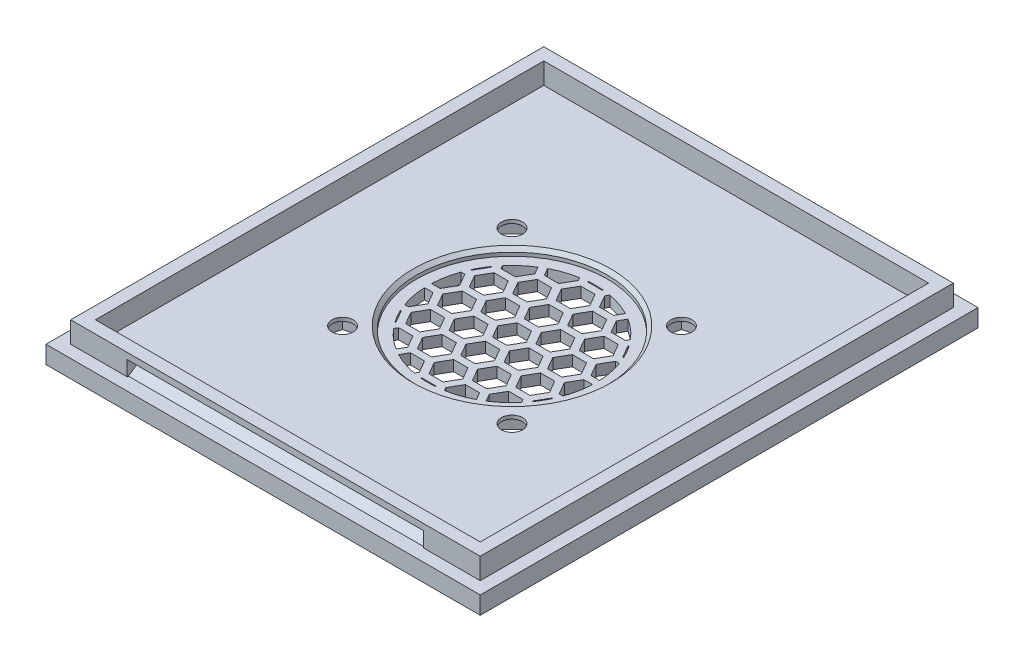
SolidWorks part; units mm, degrees
ref_plane "Front Plane" through (0, 0, 0) normal (0, 0, 1) x (1, 0, 0)
ref_plane "Top Plane" through (0, 0, 0) normal (0, 1, 0) x (1, 0, 0)
ref_plane "Right Plane" through (0, 0, 0) normal (1, 0, 0) x (0, 0, -1)
sketch "Sketch1" plane through (0, 0, 0) normal (0, 1, 0) x (1, 0, 0)
  line L0 (-15, 12) -> (-15, -12) construction
  line L1 (-30.75, -35.25) -> (30.75, -35.25)
  line L2 (-30.75, -35.25) -> (-30.75, 35.25)
  line L3 (-30.75, 35.25) -> (30.75, 35.25)
  line L4 (30.75, -35.25) -> (30.75, 35.25)
  line L5 (-30.75, -35.25) -> (30.75, 35.25) construction
  line L6 (-30.75, 35.25) -> (30.75, -35.25) construction
  line L7 (-12, -15) -> (12, -15) construction
  line L8 (15, -12) -> (15, 12) construction
  line L9 (12, 15) -> (-12, 15) construction
  line L10 (-15, 12) -> (-15, -12) construction
  line L11 (-12, -15) -> (12, -15) construction
  line L12 (15, -12) -> (15, 12) construction
  line L13 (12, 15) -> (-12, 15) construction
  arc A0 (14.2149, 1) -> (-6.2414, 12.8104) centre (0, 0) ccw construction
  arc A1 (-7.9735, 11.8104) -> (-7.9735, -11.8104) centre (0, 0) ccw construction
  arc A2 (-6.2414, -12.8104) -> (14.2149, -1) centre (0, 0) ccw construction
  arc A3 (14.2149, 1) -> (-6.2414, 12.8104) centre (0, 0) ccw construction
  arc A4 (-7.9735, 11.8104) -> (-7.9735, -11.8104) centre (0, 0) ccw construction
  arc A5 (-6.2414, -12.8104) -> (14.2149, -1) centre (0, 0) ccw construction
  arc A6 (-12, 15) -> (-15, 12) centre (-12, 12) ccw construction
  arc A7 (-15, -12) -> (-12, -15) centre (-12, -12) ccw construction
  arc A8 (12, -15) -> (15, -12) centre (12, -12) ccw construction
  arc A9 (15, 12) -> (12, 15) centre (12, 12) ccw construction
  arc A10 (-12, 15) -> (-15, 12) centre (-12, 12) ccw construction
  arc A11 (-15, -12) -> (-12, -15) centre (-12, -12) ccw construction
  arc A12 (12, -15) -> (15, -12) centre (12, -12) ccw construction
  arc A13 (15, 12) -> (12, 15) centre (12, 12) ccw construction
  circle A18 centre (12, 12) radius 1.5 construction
  circle A19 centre (12, -12) radius 1.5 construction
  circle A20 centre (-12, -12) radius 1.5 construction
  circle A21 centre (-12, 12) radius 1.5 construction
  circle A22 centre (-12, 12) radius 1.5
  circle A23 centre (-12, -12) radius 1.5
  circle A24 centre (12, -12) radius 1.5
  circle A25 centre (12, 12) radius 1.5
  point P0 (0, 0)
  dimension "D1" = 70.5
  dimension "D2" = 61.5
extrude "Boss-Extrude1" add sketch "Sketch1" along normal blind 2.5
ref_axis "Axis1" through (0, 0, 0) along (0, 0, 1)
sketch "Sketch2" plane through (0, 2.5, 0) normal (0, 1, 0) x (1, 0, 0)
  line L20 (27.25, -31.75) -> (27.25, 31.75)
  line L21 (27.25, 31.75) -> (-27.25, 31.75)
  line L22 (-27.25, 31.75) -> (-27.25, -31.75)
  line L23 (-27.25, -31.75) -> (27.25, -31.75)
  line L24 (-29, -33.5) -> (29, -33.5)
  line L25 (29, -33.5) -> (29, 33.5)
  line L26 (-29, 33.5) -> (-29, -33.5)
  line L27 (29, 33.5) -> (-29, 33.5)
  line L28 (-29, -33.5) -> (29, -33.5)
  line L29 (29, -33.5) -> (29, 33.5)
  line L30 (-29, 33.5) -> (-29, -33.5)
  line L31 (29, 33.5) -> (-29, 33.5)
  dimension "D1" = 1.75
  dimension "D2" = 1.75
extrude "Boss-Extrude2" add sketch "Sketch2" along normal blind 3
sketch "Sketch3" plane through (0, 0, 0) normal (0, -1, 0) x (1, 0, 0)
  line L1 (-11.2529, 9.2116) -> (-9.2116, 11.2529)
  line L2 (-9.2116, 11.2529) -> (-9.9588, 14.0412)
  line L3 (-9.9588, 14.0412) -> (-12.7471, 14.7884)
  line L4 (-12.7471, 14.7884) -> (-14.7884, 12.7471)
  line L5 (-14.7884, 12.7471) -> (-14.0412, 9.9588)
  line L6 (-14.0412, 9.9588) -> (-11.2529, 9.2116)
  line L7 (0, 0) -> (-6.0112, 6.0112) construction
  line L8 (9.2116, 11.2529) -> (11.2529, 9.2116)
  line L9 (11.2529, 9.2116) -> (14.0412, 9.9588)
  line L10 (14.0412, 9.9588) -> (14.7884, 12.7471)
  line L11 (14.7884, 12.7471) -> (12.7471, 14.7884)
  line L12 (12.7471, 14.7884) -> (9.9588, 14.0412)
  line L13 (9.9588, 14.0412) -> (9.2116, 11.2529)
  line L14 (11.2529, -9.2116) -> (9.2116, -11.2529)
  line L15 (9.2116, -11.2529) -> (9.9588, -14.0412)
  line L16 (9.9588, -14.0412) -> (12.7471, -14.7884)
  line L17 (12.7471, -14.7884) -> (14.7884, -12.7471)
  line L18 (14.7884, -12.7471) -> (14.0412, -9.9588)
  line L19 (14.0412, -9.9588) -> (11.2529, -9.2116)
  line L20 (-9.2116, -11.2529) -> (-11.2529, -9.2116)
  line L21 (-11.2529, -9.2116) -> (-14.0412, -9.9588)
  line L22 (-14.0412, -9.9588) -> (-14.7884, -12.7471)
  line L23 (-14.7884, -12.7471) -> (-12.7471, -14.7884)
  line L24 (-12.7471, -14.7884) -> (-9.9588, -14.0412)
  line L25 (-9.9588, -14.0412) -> (-9.2116, -11.2529)
  line L26 (0, 0) -> (-9.2116, 0) construction
  circle A0 centre (-12, 12) radius 2.5 construction
  circle A1 centre (0, 0) radius 12.2353 construction
  circle A2 centre (12, 12) radius 2.5 construction
  circle A3 centre (12, -12) radius 2.5 construction
  circle A4 centre (-12, -12) radius 2.5 construction
  circle A5 centre (12, 12) radius 1.5 construction
  point P39 (0, 0)
  dimension "D1" = 5
  dimension "D2" = 4
  dimension "D3" = 45
extrude "Cut-Extrude1" cut sketch "Sketch3" against normal blind 2
sketch "Sketch4" plane through (0, 0, 0) normal (0, -1, 0) x (1, 0, 0)
  line L0 (2.0207, 4.5) -> (1.0104, 6.25)
  line L7 (2.0207, 0) -> (1.0104, 1.75)
  line L8 (1.0104, 1.75) -> (-1.0104, 1.75)
  line L9 (-1.0104, 1.75) -> (-2.0207, 0)
  line L16 (-2.0207, 0) -> (-1.0104, -1.75)
  line L17 (-1.0104, -1.75) -> (1.0104, -1.75)
  line L18 (1.0104, -1.75) -> (2.0207, 0)
  line L27 (1.0104, 6.25) -> (-1.0104, 6.25)
  line L96 (-1.0104, 6.25) -> (-2.0207, 4.5)
  line L97 (-2.0207, 4.5) -> (-1.0104, 2.75)
  line L98 (-1.0104, 2.75) -> (1.0104, 2.75)
  line L101 (1.0104, 2.75) -> (2.0207, 4.5)
  line L102 (2.0207, 9) -> (1.0104, 10.75)
  line L103 (1.0104, 10.75) -> (-1.0104, 10.75)
  line L124 (-1.0104, 10.75) -> (-2.0207, 9)
  line L125 (-2.0207, 9) -> (-1.0104, 7.25)
  line L126 (-1.0104, 7.25) -> (1.0104, 7.25)
  line L128 (1.0104, 7.25) -> (2.0207, 9)
  line L133 (-1.0722, 11.8572) -> (-1.0104, 11.75)
  line L146 (-1.0104, 11.75) -> (1.0104, 11.75)
  line L147 (1.0104, 11.75) -> (1.0722, 11.8572)
  line L162 (2.0207, -4.5) -> (1.0104, -2.75)
  line L170 (1.0104, -2.75) -> (-1.0104, -2.75)
  line L177 (-1.0104, -2.75) -> (-2.0207, -4.5)
  line L185 (-2.0207, -4.5) -> (-1.0104, -6.25)
  line L187 (-1.0104, -6.25) -> (1.0104, -6.25)
  line L194 (1.0104, -6.25) -> (2.0207, -4.5)
  line L210 (2.0207, -9) -> (1.0104, -7.25)
  line L237 (1.0104, -7.25) -> (-1.0104, -7.25)
  line L239 (-1.0104, -7.25) -> (-2.0207, -9)
  line L263 (-2.0207, -9) -> (-1.0104, -10.75)
  line L407 (-1.0104, -10.75) -> (1.0104, -10.75)
  line L408 (1.0104, -10.75) -> (2.0207, -9)
  line L409 (1.0722, -11.8572) -> (1.0104, -11.75)
  line L411 (1.0104, -11.75) -> (-1.0104, -11.75)
  line L412 (-1.0104, -11.75) -> (-1.0722, -11.8572)
  line L443 (-2.0207, 0) -> (2.0207, 0)
  line L451 (9.8147, 4.5) -> (8.8044, 6.25)
  line L458 (9.8147, 0) -> (8.8044, 1.75)
  line L466 (8.8044, 1.75) -> (6.7836, 1.75)
  line L691 (6.7836, 1.75) -> (5.7733, 0)
  line L726 (5.7733, 0) -> (6.7836, -1.75)
  line L734 (6.7836, -1.75) -> (8.8044, -1.75)
  line L741 (8.8044, -1.75) -> (9.8147, 0)
  line L749 (8.8044, 6.25) -> (6.7836, 6.25)
  line L757 (6.7836, 6.25) -> (5.7733, 4.5)
  line L777 (5.7733, 4.5) -> (6.7836, 2.75)
  line L786 (6.7836, 2.75) -> (8.8044, 2.75)
  line L826 (8.8044, 2.75) -> (9.8147, 4.5)
  line L854 (6.3804, 10.0515) -> (5.7733, 9)
  line L861 (5.7733, 9) -> (6.7836, 7.25)
  line L862 (6.7836, 7.25) -> (8.8044, 7.25)
  line L863 (8.8044, 7.25) -> (9.0707, 7.7113)
  line L947 (9.8147, -4.5) -> (8.8044, -2.75)
  line L949 (8.8044, -2.75) -> (6.7836, -2.75)
  line L952 (6.7836, -2.75) -> (5.7733, -4.5)
  line L954 (5.7733, -4.5) -> (6.7836, -6.25)
  line L973 (6.7836, -6.25) -> (8.8044, -6.25)
  line L974 (8.8044, -6.25) -> (9.8147, -4.5)
  line L975 (9.0707, -7.7113) -> (8.8044, -7.25)
  line L977 (8.8044, -7.25) -> (6.7836, -7.25)
  line L978 (6.7836, -7.25) -> (5.7733, -9)
  line L979 (5.7733, -9) -> (6.3804, -10.0515)
  line L1151 (17.6087, 4.5) -> (16.5984, 6.25) [skipped]
  line L1152 (16.5984, 6.25) -> (14.5776, 6.25) [skipped]
  line L1153 (14.5776, 6.25) -> (13.5673, 4.5) [skipped]
  line L1154 (13.5673, 4.5) -> (14.5776, 2.75) [skipped]
  line L1155 (16.5984, 2.75) -> (17.6087, 4.5) [skipped]
  line L1156 (17.6087, 9) -> (16.5984, 10.75) [skipped]
  line L1157 (16.5984, 10.75) -> (14.5776, 10.75) [skipped]
  line L1158 (14.5776, 10.75) -> (13.5673, 9) [skipped]
  line L1159 (13.5673, 9) -> (14.5776, 7.25) [skipped]
  line L1160 (14.5776, 7.25) -> (16.5984, 7.25) [skipped]
  line L1161 (16.5984, 7.25) -> (17.6087, 9) [skipped]
  line L1165 (13.5673, 13.5) -> (14.5776, 11.75) [skipped]
  line L1166 (14.5776, 11.75) -> (16.5984, 11.75) [skipped]
  line L1167 (16.5984, 11.75) -> (17.6087, 13.5) [skipped]
  line L1168 (14.5776, 2.75) -> (16.5984, 2.75) [skipped]
  line L1169 (17.6087, -4.5) -> (16.5984, -2.75) [skipped]
  line L1170 (16.5984, -2.75) -> (14.5776, -2.75) [skipped]
  line L1171 (14.5776, -2.75) -> (13.5673, -4.5) [skipped]
  line L1172 (13.5673, -4.5) -> (14.5776, -6.25) [skipped]
  line L1173 (14.5776, -6.25) -> (16.5984, -6.25) [skipped]
  line L1174 (16.5984, -6.25) -> (17.6087, -4.5) [skipped]
  line L1175 (17.6087, -9) -> (16.5984, -7.25) [skipped]
  line L1176 (16.5984, -7.25) -> (14.5776, -7.25) [skipped]
  line L1177 (14.5776, -7.25) -> (13.5673, -9) [skipped]
  line L1178 (13.5673, -9) -> (14.5776, -10.75) [skipped]
  line L1179 (14.5776, -10.75) -> (16.5984, -10.75) [skipped]
  line L1180 (16.5984, -10.75) -> (17.6087, -9) [skipped]
  line L1181 (17.6087, -13.5) -> (16.5984, -11.75) [skipped]
  line L1182 (16.5984, -11.75) -> (14.5776, -11.75) [skipped]
  line L1183 (14.5776, -11.75) -> (13.5673, -13.5) [skipped]
  line L1187 (17.6087, 0) -> (16.5984, 1.75) [skipped]
  line L1188 (16.5984, 1.75) -> (14.5776, 1.75) [skipped]
  line L1189 (14.5776, -1.75) -> (16.5984, -1.75) [skipped]
  line L1190 (16.5984, -1.75) -> (17.6087, 0) [skipped]
  line L1194 (9.8147, -13.5) -> (8.8044, -11.75) [skipped]
  line L1195 (8.8044, 11.75) -> (9.8147, 13.5) [skipped]
  line L1199 (0, -35.25) -> (0, -15.25) construction
  line L1200 (30.75, -35.25) -> (-30.75, -35.25) construction
  line L1201 (-30.75, 35.25) -> (30.75, 35.25) construction
  line L1202 (0, -11.9055) -> (0, 11.9055) construction
  line L1203 (-10.6806, -5) -> (-10.8047, -5)
  line L1204 (-10.6806, -4) -> (-11.2135, -4)
  line L1208 (-5.7733, -9) -> (-6.3804, -10.0515)
  line L1209 (-6.7836, -7.25) -> (-5.7733, -9)
  line L1210 (-8.8044, -7.25) -> (-6.7836, -7.25)
  line L1211 (-9.0707, -7.7113) -> (-8.8044, -7.25)
  line L1212 (-8.8044, -6.25) -> (-9.8147, -4.5)
  line L1213 (-6.7836, -6.25) -> (-8.8044, -6.25)
  line L1214 (-5.7733, -4.5) -> (-6.7836, -6.25)
  line L1215 (-6.7836, -2.75) -> (-5.7733, -4.5)
  line L1216 (-8.8044, -2.75) -> (-6.7836, -2.75)
  line L1217 (-9.8147, -4.5) -> (-8.8044, -2.75)
  line L1220 (-8.8044, 7.25) -> (-9.0707, 7.7113)
  line L1221 (-6.7836, 7.25) -> (-8.8044, 7.25)
  line L1222 (-5.7733, 9) -> (-6.7836, 7.25)
  line L1223 (-6.3804, 10.0515) -> (-5.7733, 9)
  line L1226 (-8.8044, 2.75) -> (-9.8147, 4.5)
  line L1227 (-6.7836, 2.75) -> (-8.8044, 2.75)
  line L1228 (-5.7733, 4.5) -> (-6.7836, 2.75)
  line L1229 (-6.7836, 6.25) -> (-5.7733, 4.5)
  line L1230 (-8.8044, 6.25) -> (-6.7836, 6.25)
  line L1231 (-8.8044, -1.75) -> (-9.8147, 0)
  line L1232 (-6.7836, -1.75) -> (-8.8044, -1.75)
  line L1233 (-5.7733, 0) -> (-6.7836, -1.75)
  line L1234 (-6.7836, 1.75) -> (-5.7733, 0)
  line L1235 (-8.8044, 1.75) -> (-6.7836, 1.75)
  line L1236 (-9.8147, 0) -> (-8.8044, 1.75)
  line L1237 (-9.8147, 4.5) -> (-8.8044, 6.25)
  line L1238 (1.5155, -3.625) -> (6.2785, -0.875) construction
  line L1239 (6.2785, -3.625) -> (1.5155, -0.875) construction
  line L1240 (2.8866, 0.5) -> (4.9074, 0.5)
  line L1241 (1.8763, -2.25) -> (2.8866, -4)
  line L1242 (2.8866, -4) -> (4.9074, -4)
  line L1243 (4.9074, -4) -> (5.9177, -2.25)
  line L1244 (5.9177, -2.25) -> (4.9074, -0.5)
  line L1245 (4.9074, -0.5) -> (2.8866, -0.5)
  line L1246 (2.8866, -0.5) -> (1.8763, -2.25)
  line L1247 (4.9074, 0.5) -> (5.9177, 2.25)
  line L1248 (5.9177, 2.25) -> (4.9074, 4)
  line L1249 (4.9074, 4) -> (2.8866, 4)
  line L1250 (2.8866, 4) -> (1.8763, 2.25)
  line L1251 (1.8763, 2.25) -> (2.8866, 0.5)
  line L1252 (2.8866, 5) -> (4.9074, 5)
  line L1253 (4.9074, 5) -> (5.9177, 6.75)
  line L1254 (5.9177, 6.75) -> (4.9074, 8.5)
  line L1255 (4.9074, 8.5) -> (2.8866, 8.5)
  line L1256 (2.8866, 8.5) -> (1.8763, 6.75)
  line L1257 (1.8763, 6.75) -> (2.8866, 5)
  line L1258 (2.8866, 9.5) -> (4.9074, 9.5)
  line L1259 (4.9074, 9.5) -> (5.5144, 10.5515)
  line L1262 (2.1425, 11.7112) -> (1.8763, 11.25)
  line L1263 (1.8763, 11.25) -> (2.8866, 9.5)
  line L1264 (2.8866, -8.5) -> (4.9074, -8.5)
  line L1265 (4.9074, -8.5) -> (5.9177, -6.75)
  line L1266 (5.9177, -6.75) -> (4.9074, -5)
  line L1267 (4.9074, -5) -> (2.8866, -5)
  line L1268 (2.8866, -5) -> (1.8763, -6.75)
  line L1269 (1.8763, -6.75) -> (2.8866, -8.5)
  line L1272 (5.5144, -10.5515) -> (4.9074, -9.5)
  line L1273 (4.9074, -9.5) -> (2.8866, -9.5)
  line L1274 (2.8866, -9.5) -> (1.8763, -11.25)
  line L1275 (1.8763, -11.25) -> (2.1425, -11.7112)
  line L1276 (10.6806, 0.5) -> (11.895, 0.5)
  line L1277 (9.6703, -2.25) -> (10.6806, -4)
  line L1278 (10.6806, -4) -> (11.2135, -4)
  line L1281 (11.895, -0.5) -> (10.6806, -0.5)
  line L1282 (10.6806, -0.5) -> (9.6703, -2.25)
  line L1285 (11.2135, 4) -> (10.6806, 4)
  line L1286 (10.6806, 4) -> (9.6703, 2.25)
  line L1287 (9.6703, 2.25) -> (10.6806, 0.5)
  line L1288 (10.6806, 5) -> (10.8047, 5)
  line L1292 (9.7323, 6.8574) -> (9.6703, 6.75)
  line L1293 (9.6703, 6.75) -> (10.6806, 5)
  line L1303 (10.8047, -5) -> (10.6806, -5)
  line L1304 (10.6806, -5) -> (9.6703, -6.75)
  line L1305 (9.6703, -6.75) -> (9.7323, -6.8574)
  line L1312 (10.6806, 9.5) -> (12.7014, 9.5) [skipped]
  line L1313 (12.7014, 9.5) -> (13.7117, 11.25) [skipped]
  line L1316 (9.6703, 11.25) -> (10.6806, 9.5) [skipped]
  line L1317 (10.6806, 13) -> (9.6703, 11.25) [skipped]
  line L1318 (13.7117, 6.75) -> (12.7014, 8.5) [skipped]
  line L1319 (12.7014, -9.5) -> (10.6806, -9.5) [skipped]
  line L1320 (10.6806, -9.5) -> (9.6703, -11.25) [skipped]
  line L1321 (9.6703, -11.25) -> (10.6806, -13) [skipped]
  line L1324 (13.7117, -11.25) -> (12.7014, -9.5) [skipped]
  line L1325 (12.7014, -8.5) -> (13.7117, -6.75) [skipped]
  line L1326 (-9.6703, -6.75) -> (-9.7323, -6.8574)
  line L1327 (-10.6806, -5) -> (-9.6703, -6.75)
  line L1331 (-9.6703, 6.75) -> (-10.6806, 5)
  line L1332 (-9.7323, 6.8574) -> (-9.6703, 6.75)
  line L1335 (-10.6806, 5) -> (-10.8047, 5)
  line L1336 (-9.6703, 2.25) -> (-10.6806, 0.5)
  line L1337 (-10.6806, 4) -> (-9.6703, 2.25)
  line L1338 (-11.2135, 4) -> (-10.6806, 4)
  line L1341 (-10.6806, -0.5) -> (-9.6703, -2.25)
  line L1342 (-11.895, -0.5) -> (-10.6806, -0.5)
  line L1346 (-9.6703, -2.25) -> (-10.6806, -4)
  line L1347 (-10.6806, 0.5) -> (-11.895, 0.5)
  line L1348 (-1.8763, -11.25) -> (-2.1425, -11.7112)
  line L1349 (-2.8866, -9.5) -> (-1.8763, -11.25)
  line L1350 (-4.9074, -9.5) -> (-2.8866, -9.5)
  line L1351 (-5.5144, -10.5515) -> (-4.9074, -9.5)
  line L1354 (-1.8763, -6.75) -> (-2.8866, -8.5)
  line L1355 (-2.8866, -5) -> (-1.8763, -6.75)
  line L1356 (-4.9074, -5) -> (-2.8866, -5)
  line L1357 (-5.9177, -6.75) -> (-4.9074, -5)
  line L1358 (-4.9074, -8.5) -> (-5.9177, -6.75)
  line L1359 (-2.8866, -8.5) -> (-4.9074, -8.5)
  line L1360 (-1.8763, 11.25) -> (-2.8866, 9.5)
  line L1361 (-2.1425, 11.7112) -> (-1.8763, 11.25)
  line L1364 (-4.9074, 9.5) -> (-5.5144, 10.5515)
  line L1365 (-2.8866, 9.5) -> (-4.9074, 9.5)
  line L1366 (-1.8763, 6.75) -> (-2.8866, 5)
  line L1367 (-2.8866, 8.5) -> (-1.8763, 6.75)
  line L1368 (-4.9074, 8.5) -> (-2.8866, 8.5)
  line L1369 (-5.9177, 6.75) -> (-4.9074, 8.5)
  line L1370 (-4.9074, 5) -> (-5.9177, 6.75)
  line L1371 (-2.8866, 5) -> (-4.9074, 5)
  line L1372 (-1.8763, 2.25) -> (-2.8866, 0.5)
  line L1373 (-2.8866, 4) -> (-1.8763, 2.25)
  line L1374 (-4.9074, 4) -> (-2.8866, 4)
  line L1375 (-5.9177, 2.25) -> (-4.9074, 4)
  line L1376 (-4.9074, 0.5) -> (-5.9177, 2.25)
  line L1377 (-2.8866, -0.5) -> (-1.8763, -2.25)
  line L1378 (-4.9074, -0.5) -> (-2.8866, -0.5)
  line L1379 (-5.9177, -2.25) -> (-4.9074, -0.5)
  line L1380 (-4.9074, -4) -> (-5.9177, -2.25)
  line L1381 (-2.8866, -4) -> (-4.9074, -4)
  line L1382 (-1.8763, -2.25) -> (-2.8866, -4)
  line L1383 (-2.8866, 0.5) -> (-4.9074, 0.5)
  line L1384 (0, 15.25) -> (0, 35.25) construction
  line L1385 (4.9074, 13) -> (2.8866, 13) [skipped]
  line L1386 (5.9177, 11.25) -> (4.9074, 13) [skipped]
  line L1387 (12.7014, 5) -> (13.7117, 6.75) [skipped]
  line L1388 (13.7117, 2.25) -> (12.7014, 4) [skipped]
  line L1389 (12.7014, 0.5) -> (13.7117, 2.25) [skipped]
  line L1390 (13.7117, -6.75) -> (12.7014, -5) [skipped]
  line L1391 (13.5673, 0) -> (14.5776, -1.75) [skipped]
  line L1392 (14.5776, 1.75) -> (13.5673, 0) [skipped]
  line L1393 (13.7117, -2.25) -> (13.2065, -1.375) [skipped]
  line L1394 (12.7014, -4) -> (13.2065, -3.125) [skipped]
  line L1395 (12.7014, 8.5) -> (10.6806, 8.5) [skipped]
  line L1396 (8.8044, 10.75) -> (7.794, 10.75) [skipped]
  line L1397 (9.8147, 9) -> (9.3095, 9.875) [skipped]
  line L1398 (5.7733, 13.5) -> (6.7836, 11.75) [skipped]
  line L1399 (6.7836, 11.75) -> (8.8044, 11.75) [skipped]
  line L1400 (-2.0207, -13.5) -> (-1.5155, -14.375) [skipped]
  line L1401 (1.0104, -15.25) -> (2.0207, -13.5) [skipped]
  line L1402 (0, -15.25) -> (1.0104, -15.25) [skipped]
  line L1403 (2.8866, -13) -> (4.9074, -13) [skipped]
  line L1404 (4.9074, -13) -> (5.9177, -11.25) [skipped]
  line L1405 (6.7836, -11.75) -> (5.7733, -13.5) [skipped]
  line L1406 (8.8044, -11.75) -> (6.7836, -11.75) [skipped]
  line L1407 (7.794, -10.75) -> (8.8044, -10.75) [skipped]
  line L1408 (8.8044, -10.75) -> (9.8147, -9) [skipped]
  line L1409 (10.6806, -8.5) -> (12.7014, -8.5) [skipped]
  line L1410 (-1.0104, 15.25) -> (-2.0207, 13.5) [skipped]
  line L1411 (1.5155, 14.375) -> (1.0104, 15.25) [skipped]
  line L1412 (1.0104, 15.25) -> (0, 15.25) [skipped]
  circle A1 centre (0, 4.5) radius 1.75 construction
  arc A2 (-6.3804, 10.0515) -> (-9.0707, 7.7113) centre (0, 0) ccw
  circle A3 centre (0, 0) radius 1.75 construction
  circle A4 centre (0, 9) radius 1.75 construction
  arc A5 (-0.6771, 11.8863) -> (0.6771, 11.8863) centre (0, 13.5) ccw construction
  circle A6 centre (0, -4.5) radius 1.75 construction
  circle A7 centre (0, -9) radius 1.75 construction
  arc A8 (0.6771, -11.8863) -> (-0.6771, -11.8863) centre (0, -13.5) ccw construction
  circle A9 centre (7.794, 4.5) radius 1.75 construction
  circle A10 centre (7.794, 0) radius 1.75 construction
  arc A11 (6.3904, 10.0452) -> (9.029, 7.7601) centre (7.794, 9) ccw construction
  arc A12 (-9.7323, 6.8574) -> (-10.8047, 5) centre (0, 0) ccw
  circle A13 centre (7.794, -4.5) radius 1.75 construction
  arc A14 (9.029, -7.7601) -> (6.3904, -10.0452) centre (7.794, -9) ccw construction
  circle A15 centre (-7.794, -4.5) radius 1.75 construction
  arc A16 (-6.3904, 10.0452) -> (-9.029, 7.7601) centre (-7.794, 9) cw construction
  circle A17 centre (-7.794, 0) radius 1.75 construction
  circle A18 centre (-7.794, 4.5) radius 1.75 construction
  circle A19 centre (3.897, -2.25) radius 1.75 construction
  arc A20 (11.8945, -0.5119) -> (11.2349, -3.9395) centre (11.691, -2.25) ccw construction
  arc A21 (-11.8945, -0.5119) -> (-11.2349, -3.9395) centre (-11.691, -2.25) cw construction
  circle A22 centre (-3.897, -2.25) radius 1.75 construction
  circle A23 centre (15.588, 4.5) radius 1.75 construction
  circle A24 centre (15.588, 9) radius 1.75 construction
  circle A25 centre (15.588, 13.5) radius 1.75 construction
  circle A26 centre (15.588, -4.5) radius 1.75 construction
  circle A27 centre (15.588, -9) radius 1.75 construction
  circle A28 centre (15.588, -13.5) radius 1.75 construction
  circle A29 centre (15.588, 0) radius 1.75 construction
  circle A30 centre (7.794, -13.5) radius 1.75 construction
  circle A31 centre (7.794, 13.5) radius 1.75 construction
  arc A33 (-11.2135, 4) -> (-11.895, 0.5) centre (0, 0) ccw
  arc A34 (-11.895, -0.5) -> (-11.2135, -4) centre (0, 0) ccw
  arc A35 (-10.8047, -5) -> (-9.7323, -6.8574) centre (0, 0) ccw
  arc A36 (-9.0707, -7.7113) -> (-6.3804, -10.0515) centre (0, 0) ccw
  arc A37 (-9.029, -7.7601) -> (-6.3904, -10.0452) centre (-7.794, -9) cw construction
  arc A38 (-5.5144, -10.5515) -> (-2.1425, -11.7112) centre (0, 0) ccw
  arc A39 (-1.0722, -11.8572) -> (1.0722, -11.8572) centre (0, 0) ccw
  arc A40 (2.1425, -11.7112) -> (5.5144, -10.5515) centre (0, 0) ccw
  arc A41 (6.3804, -10.0515) -> (9.0707, -7.7113) centre (0, 0) ccw
  arc A42 (9.7323, -6.8574) -> (10.8047, -5) centre (0, 0) ccw
  arc A43 (11.2135, -4) -> (11.895, -0.5) centre (0, 0) ccw
  arc A44 (11.895, 0.5) -> (11.2135, 4) centre (0, 0) ccw
  arc A45 (10.8047, 5) -> (9.7323, 6.8574) centre (0, 0) ccw
  arc A46 (9.0707, 7.7113) -> (6.3804, 10.0515) centre (0, 0) ccw
  arc A47 (5.5144, 10.5515) -> (2.1425, 11.7112) centre (0, 0) ccw
  arc A48 (1.0722, 11.8572) -> (-1.0722, 11.8572) centre (0, 0) ccw
  arc A49 (-2.1425, 11.7112) -> (-5.5144, 10.5515) centre (0, 0) ccw
  point P294 (11.2878, 0.5)
  dimension "D1" = 7.794
  dimension "D3" = 4.0415
  dimension "D4" = 4
  dimension "D2" = 3.5
  dimension "D9" = 3.5
  dimension "D16" = 120
  dimension "D5" = 4
  dimension "D6" = 3
  dimension "D7" = 4.5
  dimension "D8" = 4.5
  dimension "D13" = 1
  dimension "D14" = 1
  dimension "D15" = 7.794
  dimension "D17" = 120
  dimension "D18" = 120
  dimension "D19" = 120
  dimension "D20" = 120
  dimension "D21" = 120
  dimension "D12" = 4
  dimension "D11" = 3
  dimension "D10" = 2
sketch "Sketch6" plane through (0, 2.5, 0) normal (0, 1, 0) x (1, 0, 0)
  circle A0 centre (0, 0) radius 13.5
  dimension "D1" = 27
extrude "Cut-Extrude7" cut sketch "Sketch6" against normal blind 1
chamfer "Chamfer1" distance 0.5 angle 45 1 edges at (0, 2.5, 13.5)
extrude "Cut-Extrude8" cut sketch "Sketch4" against normal up to next (1.5 mm away) contours L1288 A45 L1292 L1293 | L1276 A44 L1285 L1286 L1287 | L786 L826 L451 L749 L757 L777 | L863 A46 L854 L861 L862 | L734 L741 L458 L466 L691 L726 | L1278 A43 L1281 L1282 L1277 | L973 L974 L947 L949 L952 L954 | L979 A41 L975 L977 L978 | L1275 A40 L1272 L1273 L1274 | L1268 L1269 L1264 L1265 L1266 L1267 | L1245 L1246 L1241 L1242 L1243 L1244 | L1250 L1251 L1240 L1247 L1248 L1249 | L1256 L1257 L1252 L1253 L1254 L1255 | L1259 A47 L1262 L1263 L1258 | L126 L128 L102 L103 L124 L125 | L98 L101 L0 L27 L96 L97 | L9 L443 L7 L8 | L443 L16 L17 L18 | L187 L194 L162 L170 L177 L185 | L407 L408 L210 L237 L239 L263 | L1351 A38 L1348 L1349 L1350 | L1359 L1354 L1355 L1356 L1357 L1358 | L1382 L1377 L1378 L1379 L1380 L1381 | L1383 L1372 L1373 L1374 L1375 L1376 | L1371 L1366 L1367 L1368 L1369 L1370 | L1361 A49 L1364 L1365 L1360 | L1223 A2 L1220 L1221 L1222 | L1237 L1226 L1227 L1228 L1229 L1230 | L1236 L1231 L1232 L1233 L1234 L1235 | L1217 L1212 L1213 L1214 L1215 L1216 | L1211 A36 L1208 L1209 L1210 | L1342 A34 L1204 L1346 L1341 | L1338 A33 L1347 L1336 L1337 | L1304 L1305 A42 L1303 | L146 L147 A48 L133 | L411 L412 A39 L409 | A35 L1326 L1327 L1203 | A12 L1335 L1331 L1332 region at (0, 0, 4.5) region at (0, 0, 0.7778) region at (0, 0, -0.7778) region at (0, 0, 9) region at (0, 0, -4.5) region at (0, 0, -9) region at (7.794, 0, 4.5) region at (7.794, 0, 0) region at (7.2795, 0, 8.378) region at (7.794, 0, -4.5) region at (7.2795, 0, -8.378) region at (-10.8952, 0, -2.1154) region at (-7.2795, 0, -8.378) region at (-7.794, 0, -4.5) region at (-7.2795, 0, 8.378) region at (-7.794, 0, 4.5) region at (-7.794, 0, 0) region at (3.897, 0, 2.25) region at (3.897, 0, -2.25) region at (3.897, 0, 6.75) region at (3.6156, 0, 10.4933) region at (3.897, 0, -6.75) region at (3.6156, 0, -10.4933) region at (10.8952, 0, 2.1154) region at (10.8952, 0, -2.1154) region at (10.2373, 0, 5.9107) region at (-10.8952, 0, 2.1154) region at (-3.6156, 0, -10.4933) region at (-3.897, 0, -6.75) region at (-3.6156, 0, 10.4933) region at (-3.897, 0, 6.75) region at (-3.897, 0, 2.25) region at (-3.897, 0, -2.25)
sketch "Sketch7" plane through (0, 0, 0) normal (1, 0, 0) x (0, 0, -1)
  line L0 (-33.325, 2.5) -> (-33.6, 2.5)
  line L1 (-33.5, 2.5) -> (-33.5, 4.5) construction
  line L2 (-33.5, 4.5) -> (-32.0639, 3.5) construction
  line L3 (-32.0639, 3.5) -> (-33.5, 2.5) construction
  line L4 (-31.8889, 3.5) -> (-33.325, 2.5)
  line L5 (-33.6, 2.5) -> (-33.6, 4.6915)
  line L6 (-33.6, 4.6915) -> (-31.8889, 3.5)
  line L7 (-32.2389, 3.5) -> (-33.4, 2.6915) construction
  line L8 (-33.4, 2.6915) -> (-33.4, 4.3085) construction
  line L9 (-33.4, 4.3085) -> (-32.2389, 3.5) construction
  line L10 (31.75, 2.5) -> (-31.75, 2.5) construction
  line L11 (31.75, 2.5) -> (-31.75, 2.5) construction
  line L12 (-31.8889, 3.5) -> (-33.6, 2.3085) construction
  line L13 (-33.6, 2.3085) -> (-33.6, 4.6915) construction
  line L14 (0, 0) -> (0, 7.8763) construction
  line L15 (32.0639, 3.5) -> (33.5, 2.5) construction
  line L16 (33.5, 4.5) -> (32.0639, 3.5) construction
  line L17 (33.5, 2.5) -> (33.5, 4.5) construction
  line L18 (33.4, 4.3085) -> (32.2389, 3.5) construction
  line L19 (33.4, 2.6915) -> (33.4, 4.3085) construction
  line L20 (32.2389, 3.5) -> (33.4, 2.6915) construction
  line L21 (33.6, 4.6915) -> (31.8889, 3.5)
  line L22 (33.6, 2.5) -> (33.6, 4.6915)
  line L23 (31.8889, 3.5) -> (33.325, 2.5)
  line L24 (33.325, 2.5) -> (33.6, 2.5)
  dimension "D1" = 1.75
  dimension "D2" = 1.75
  dimension "D3" = 0.1
  dimension "D4" = 0.1
extrude "Cut-Extrude9" cut sketch "Sketch7" against normal mid plane 42
sketch "Sketch9" [suppressed] plane through (0, 0, 0) normal (1, 0, 0) x (0, 0, -1)
  line L3 (30.75, 3.9255) -> (30.75, 3.0745)
  line L4 (31.75, 5.5) -> (31.75, 2.5) construction
  line L5 (30.1389, 3.5) -> (32.7536, 1.6793)
  line L6 (32.9286, 5.4425) -> (30.1389, 3.5)
  line L7 (30.75, 3.0745) -> (31.575, 2.5)
  line L8 (31.75, 4.6219) -> (30.75, 3.9255)
  line L9 (33.6389, 3.5) -> (33.8964, 3.3207)
  line L10 (34.0714, 3.8012) -> (33.6389, 3.5)
  line L11 (33.6389, 3.5) -> (33.8964, 3.3207)
  line L12 (34.0714, 3.8012) -> (33.6389, 3.5)
  line L13 (31.75, 4.6219) -> (31.75, 2.5)
  line L14 (31.75, 2.5) -> (31.575, 2.5)
  line L15 (35.25, 2.5) -> (-35.25, 2.5) construction
  line L16 (31.75, 5.5) -> (31.75, 2.5) construction
  line L17 (0, 0) -> (0, 20.3012) construction
  line L18 (-31.75, 2.5) -> (-31.575, 2.5)
  line L19 (-31.75, 4.6219) -> (-31.75, 2.5)
  line L20 (-31.75, 4.6219) -> (-30.75, 3.9255)
  line L21 (-30.75, 3.0745) -> (-31.575, 2.5)
  line L22 (-30.75, 3.9255) -> (-30.75, 3.0745)
  dimension "D3" = 1
  dimension "D1" = 1
  dimension "D2" = 1
extrude "Boss-Extrude3" [suppressed] add sketch "Sketch9" along normal mid plane 42 contours L14 L13 L8 L3 L7 | L22 L20 L19 L18 L21
sketch "Sketch10" [suppressed] plane through (0, 2.5, 0) normal (0, 1, 0) x (1, 0, 0)
  line L0 (-30.75, -35.25) -> (30.75, -35.25) construction
  line L1 (-22.5, -35.25) -> (22.5, -35.25)
  line L2 (-22.5, -35.25) -> (-22.5, -34.5)
  line L3 (-21.5, -33.5) -> (21.5, -33.5)
  line L4 (22.5, -35.25) -> (22.5, -34.5)
  line L5 (21, -33.5) -> (29, -33.5) construction
  line L6 (0, 0) -> (37.4396, 0) construction
  line L7 (22.5, 35.25) -> (22.5, 34.5)
  line L8 (-21.5, 33.5) -> (21.5, 33.5)
  line L9 (-22.5, 35.25) -> (-22.5, 34.5)
  line L10 (-22.5, 35.25) -> (22.5, 35.25)
  line L11 (-22.5, -34.5) -> (-21.5, -33.5)
  line L12 (22.5, -34.5) -> (21.5, -33.5)
  line L13 (-22.5, 34.5) -> (-21.5, 33.5)
  line L14 (22.5, 34.5) -> (21.5, 33.5)
  point P1 (22.5, -33.5)
  point P2 (-22.5, -33.5)
  point P8 (0, -35.25)
  point P13 (22.5, 33.5)
  point P14 (-22.5, 33.5)
  dimension "D1" = 45
extrude "Cut-Extrude10" [suppressed] cut sketch "Sketch10" against normal blind 1
chamfer "Chamfer2" [suppressed] distance 0.5 angle 45
